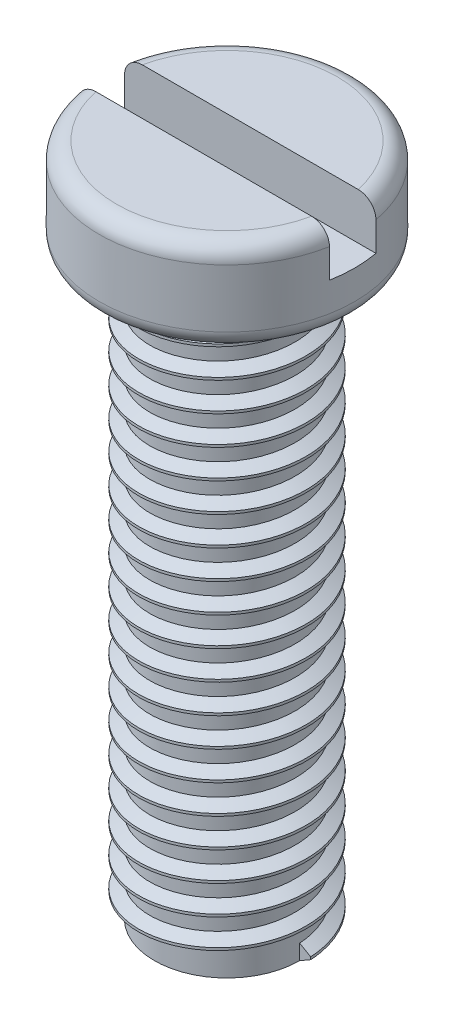
SolidWorks part; units mm, degrees
ref_plane "Front Plane" through (0, 0, 0) normal (0, 0, 1) x (1, 0, 0)
ref_plane "Top Plane" through (0, 0, 0) normal (0, 1, 0) x (1, 0, 0)
ref_plane "Right Plane" through (0, 0, 0) normal (1, 0, 0) x (0, 0, -1)
sketch "Sketch1" plane through (0, 0, 0) normal (0, 0, 1) x (1, 0, 0)
  line L1 (0, 0) -> (2.2, 0)
  line L2 (0, 0) -> (0, 1.6)
  line L3 (0, 1.6) -> (2.2, 1.6)
  line L4 (2.2, 0) -> (2.2, 1.6)
  dimension "D2" = 2.2
  dimension "D3" = 1.6
revolve "Revolve1" add sketch "Sketch1" angle 360 about L2
fillet "Fillet1" radius 0.3 2 edges at (0, 0, -2.2) (0, 1.6, -2.2)
sketch "Sketch4" plane through (0, 1.6, 0) normal (0, 1, 0) x (1, 0, 0)
  line L1 (-2.2, -0.4) -> (2.2, -0.4)
  line L2 (-2.2, -0.4) -> (-2.2, 0.4)
  line L3 (-2.2, 0.4) -> (2.2, 0.4)
  line L4 (2.2, -0.4) -> (2.2, 0.4)
  line L5 (-2.2, -0.4) -> (2.2, 0.4) construction
  line L6 (-2.2, 0.4) -> (2.2, -0.4) construction
  circle A0 centre (0, 0) radius 2.2 construction
  point P0 (0, 0)
  dimension "D1" = 0.8
extrude "Cut-Extrude1" cut sketch "Sketch4" against normal blind 0.8
sketch "Sketch3" plane through (0, 0, 0) normal (0, -1, 0) x (1, 0, 0)
  circle A0 centre (0, 0) radius 1.25
  dimension "D1" = 2.5
extrude "Boss-Extrude1" add sketch "Sketch3" along normal blind 10
thread "Thread1" pitch 0.35 start angle 0, offset 0, length 10, pitch 0.5, diameter 2.5
ref_plane "Plane2" through (1.25, 0, 0) normal (0, 0, 1) x (1, 0, 0)
sketch "Thread Profile1" plane through (1.25, 0, 0) normal (0, 0, 1) x (1, 0, 0)
  line L0 (0, 0) -> (0, 0.35) construction
  line L1 (0, 0) -> (0.1894, 0.1094)
  line L2 (0.1894, 0.1094) -> (0.1894, 0.1531)
  line L3 (0.1894, 0.1531) -> (0, 0.2625)
  line L4 (0.1894, 0.1312) -> (0, 0.1312) construction
  line L11 (0, 0) -> (0, 0.2625)
  point P2 (0, 0)
  dimension "Pitch" = 0.35
  dimension "Profile_Angle" = 60
  dimension "Profile_Land" = 0.0437
  dimension "Profile_Height" = 0.1894
